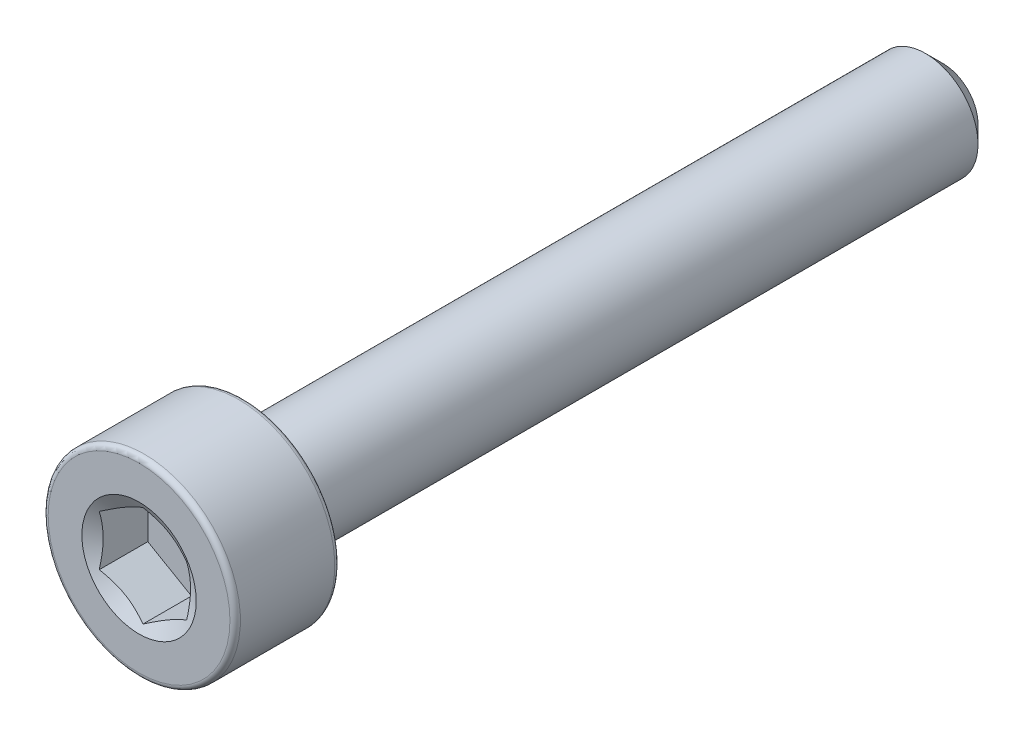
SolidWorks part; units mm, degrees
ref_plane "Front Plane" through (0, 0, 0) normal (0, 0, 1) x (1, 0, 0)
ref_plane "Top Plane" through (0, 0, 0) normal (0, 1, 0) x (1, 0, 0)
ref_plane "Right Plane" through (0, 0, 0) normal (1, 0, 0) x (0, 0, -1)
sketch "Sketch1" plane through (0, 0, 0) normal (1, 0, 0) x (0, 0, -1)
  line L0 (11.5, 0) -> (-11.5, 0) construction
  line L1 (-8.5, 2.75) -> (-8.5, -2.75) construction
  line L2 (11.5, 1.5) -> (11.5, -1.5) construction
  line L3 (11.4688, 1.5541) -> (11.7188, 1.1211) construction
  line L4 (11.6875, 1.1752) -> (11.75, 1.1752) construction
  line L5 (11.7188, 1.1211) -> (11.9688, 1.5541) construction
  line L6 (11.9688, 1.5541) -> (11.4688, 1.5541) construction
  line L7 (11.7188, 1.1752) -> (11.7188, 1.1211) construction
  line L8 (11.7188, 1.5541) -> (11.7188, 1.5) construction
  line L9 (11.9375, 1.5) -> (11.5, 1.5) construction
  point P4 (-8.5, 0)
  point P6 (-8.5, 1.25)
  point P7 (10.25, -1.5)
  point P20 (11.7188, 1.5271)
  dimension "Head Height" = 3
  dimension "Head Diameter" = 5.5
  dimension "Drive Size" = 2.5
  dimension "Length" = 20
  dimension "Thread Size" = 3
  dimension "Thread Pitch" = 0.5
  dimension "Pitch/8" = 0.0625
  dimension "Thread Note" = 1.25
sketch "Sketch2" plane through (0, 0, 0) normal (1, 0, 0) x (0, 0, -1)
  line L0 (11.5, 0) -> (11.5, 1)
  line L1 (11.5, 1.5) -> (11.5, -1.5) construction
  line L2 (11.5, 1) -> (11, 1.5)
  line L3 (11, 1.5) -> (-8.5, 1.5)
  line L4 (-8.5, 1.5) -> (-8.5, 2.6)
  line L5 (-8.65, 2.75) -> (-11.35, 2.75)
  line L6 (-11.5, 2.6) -> (-11.5, 0)
  line L7 (11.5, 0) -> (-11.5, 0) construction
  line L8 (-11.5, 0) -> (11.5, 0)
  arc A0 (-8.5, 2.6) -> (-8.65, 2.75) centre (-8.65, 2.6) ccw
  arc A1 (-11.35, 2.75) -> (-11.5, 2.6) centre (-11.35, 2.6) ccw
  point P19 (-8.5, 2.75)
  dimension "D3" = 0.15
  dimension "D1" = 0.5
  dimension "D2" = 45
revolve "Revolve1" add sketch "Sketch2" angle 360 about L0
sketch "Sketch3" plane through (0, 0, 0) normal (0, 0, 1) x (1, 0, 0)
  line L1 (-1.25, 0.7217) -> (-1.25, -0.7217)
  line L2 (-1.25, -0.7217) -> (0, -1.4434)
  line L3 (0, -1.4434) -> (1.25, -0.7217)
  line L4 (1.25, -0.7217) -> (1.25, 0.7217)
  line L5 (1.25, 0.7217) -> (0, 1.4434)
  line L6 (0, 1.4434) -> (-1.25, 0.7217)
  circle A0 centre (0, 0) radius 1.25 construction
  circle A1 centre (0, 0) radius 2.75 construction
extrude "Cut-Extrude1" cut sketch "Sketch3" against normal blind 1.5 from vertex starting at point (0, 0, 11.5)
sketch "Sketch4" plane through (0, 0, 11.5) normal (0, 0, 1) x (1, 0, 0)
  line L0 (0, 1.4434) -> (0, 1.8289) construction
  line L1 (0, 1.8289) -> (0, 2.2145) construction
  line L2 (0, 2.2145) -> (0, 2.6) construction
  circle A0 centre (0, 0) radius 1.6361
  point P12 (0, 1.6361)
extrude "Cut-Extrude2" cut sketch "Sketch4" against normal through all draft 60
split "Split1" [suppressed] bodies to split 106 112
sketch "Sketch5" [suppressed] plane through (0, 0, 0) normal (1, 0, 0) x (0, 0, -1)
  line L0 (11.6875, 1.1752) -> (11.75, 1.1752)
  line L1 (11.75, 1.1752) -> (11.9531, 1.5271)
  line L2 (11.9531, 1.5271) -> (11.4844, 1.5271)
  line L3 (11.4844, 1.5271) -> (11.6875, 1.1752)
  line L4 (11.4688, 1.5541) -> (11.7188, 1.1211) construction
sketch "Sketch6" [suppressed] plane through (0, 0, -11.5) normal (0, 0, -1) x (-1, 0, 0)
  circle A0 centre (0, 0) radius 1.5
curve "Helix/Spiral1" [suppressed] pitch 0.5 height 20.5 turns 41
sweep "Cut-Sweep1" [suppressed] cut profiles "Sketch5" path "Helix/Spiral1"
sketch "Sketch7" [suppressed] plane through (0, 0, 8.5) normal (0, 0, -1) x (-1, 0, 0)
  circle A0 centre (0, 0) radius 1.5508
  circle A1 centre (0, 0) radius 1.5 construction
  dimension "D1" = 0.0508
extrude "Boss-Extrude1" [suppressed] add sketch "Sketch7" along normal blind 1.5 draft 20 and the other way blind 0.3
equation "\"Pitch/8@Sketch1\" = \"Thread Pitch@Sketch1\" / 8"
equation "\"Thread Note@Sketch1\" = \"Thread Pitch@Sketch1\" * 2.5"
equation "\"D1@Sketch2\" = \"Thread Pitch@Sketch1\""
equation "\"D3@Sketch2\"=\"Head Height@Sketch1\"*.05"
equation "\"D1@Cut-Extrude1\" = \"Head Height@Sketch1\" * .5"
equation "\"D3@Helix/Spiral1\" = \"Length@Sketch1\" + \"Thread Pitch@Sketch1\""
equation "\"D4@Helix/Spiral1\" = \"Thread Pitch@Sketch1\""
equation "\"D2@Boss-Extrude1\" = \"Head Height@Sketch1\" * .1"
equation "\"D1\"= \"Thread Size@Sketch1\" * .4"
equation "\"D1@Boss-Extrude1\" = \"Thread Pitch@Sketch1\" * 3"
